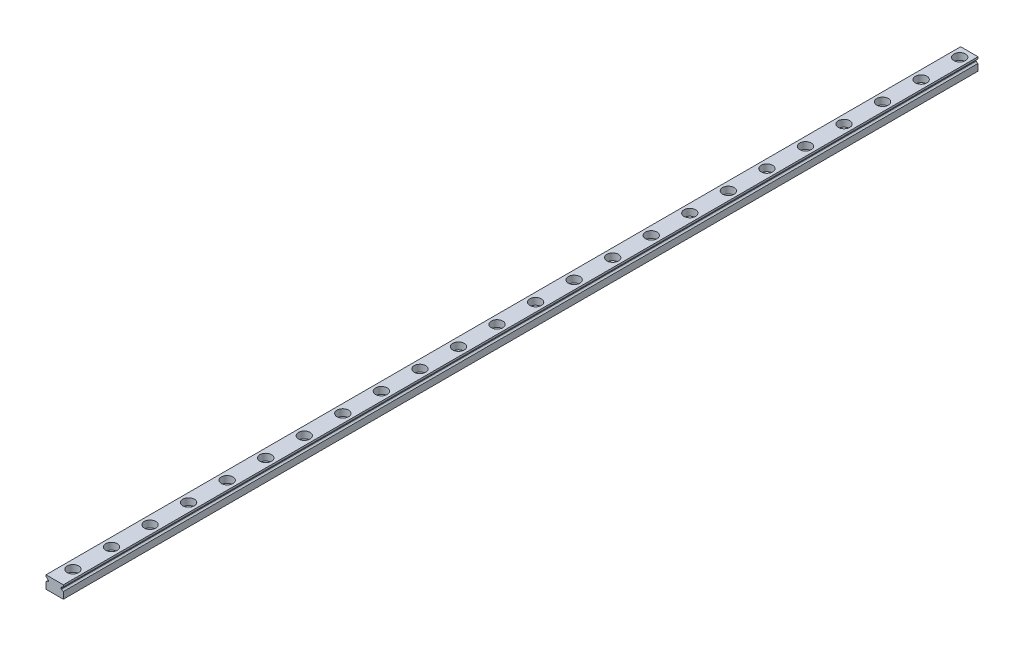
SolidWorks part; units mm, degrees
ref_plane "Спереди" through (0, 0, 0) normal (0, 0, 1) x (1, 0, 0)
ref_plane "Сверху" through (0, 0, 0) normal (0, 1, 0) x (1, 0, 0)
ref_plane "Справа" through (0, 0, 0) normal (1, 0, 0) x (0, 0, -1)
sketch "Sketch1" plane through (0, 0, 0) normal (0, 0, 1) x (1, 0, 0)
  line L0 (0, 0) -> (0, 5.7299) construction
  line L1 (-4.5, -3.25) -> (4.5, -3.25)
  line L2 (-4.5, -3.25) -> (-4.5, 0.25)
  line L3 (-4.5, 3.25) -> (4.5, 3.25)
  line L4 (4.5, -3.25) -> (4.5, 0.25)
  line L5 (-4.5, -3.25) -> (4.5, 3.25) construction
  line L6 (-4.5, 3.25) -> (4.5, -3.25) construction
  line L7 (-4.5, 2.25) -> (-4.5, 3.25)
  line L8 (-3.564, 0.898) -> (-3.2351, 0.898)
  line L9 (3.564, 0.898) -> (3.2351, 0.898)
  line L10 (-3.564, 1.602) -> (-3.2351, 1.602)
  line L11 (-3.2351, 0.898) -> (-3.2351, 1.602)
  line L12 (3.2351, 0.898) -> (3.2351, 1.602)
  line L13 (3.564, 1.602) -> (3.2351, 1.602)
  line L14 (4.5, 2.25) -> (4.5, 3.25)
  arc A0 (-3.564, 1.602) -> (-4.5, 2.25) centre (-4.5, 1.25) ccw
  arc A1 (-4.5, 0.25) -> (-3.564, 0.898) centre (-4.5, 1.25) ccw
  arc A2 (4.5, 0.25) -> (3.564, 0.898) centre (4.5, 1.25) cw
  arc A3 (3.564, 1.602) -> (4.5, 2.25) centre (4.5, 1.25) cw
  point P0 (0, 0)
  dimension "D3" = 1
  dimension "D1" = 9
  dimension "D2" = 6.5
  dimension "D4" = 2
extrude "Extrude1" add sketch "Sketch1" along normal blind 600
sketch "Sketch2" plane through (0, 3.25, 0) normal (0, 1, 0) x (1, 0, 0)
  line L0 (4.5, 0) -> (-4.5, 0) construction
  circle A0 centre (0, -5) radius 1.75
  circle A1 centre (0, -5) radius 3
  dimension "D1" = 3.5
  dimension "D2" = 6
  dimension "D3" = 5
extrude "Extrude2" cut sketch "Sketch2" against normal blind 3.5 contours A1
extrude "Extrude3" cut sketch "Sketch" against normal through all contours A0
sketch "Sketch" plane through (0, 3.25, 0) normal (0, 1, 0) x (1, 0, 0) same geometry as "Sketch2"
pattern_linear "LPattern1" count 30 spacing 20 along (0, 0, 1) of "Extrude2", "Extrude3"
sketch "Sketch3" plane through (0, 3.25, 0) normal (0, 1, 0) x (1, 0, 0)
  line L0 (4.5, 0) -> (-4.5, 0) construction
  line L1 (4.5, -474.472) -> (-4.5, -474.472)
  line L2 (4.5, -474.472) -> (4.5, -600)
  line L3 (4.5, -600) -> (-4.5, -600)
  line L4 (-4.5, -474.472) -> (-4.5, -600)
  line L5 (4.5, -474.472) -> (-4.5, -600) construction
  line L6 (4.5, -600) -> (-4.5, -474.472) construction
  line L7 (4.5, -600) -> (-4.5, -600) construction
  line L8 (-4.5, -600) -> (-4.5, 0) construction
  line L9 (4.5, -600) -> (4.5, 0) construction
  point P0 (0, -537.236)
  dimension "D1" = 474.472
extrude "Cut-Extrude1" cut sketch "Sketch3" against normal through all
